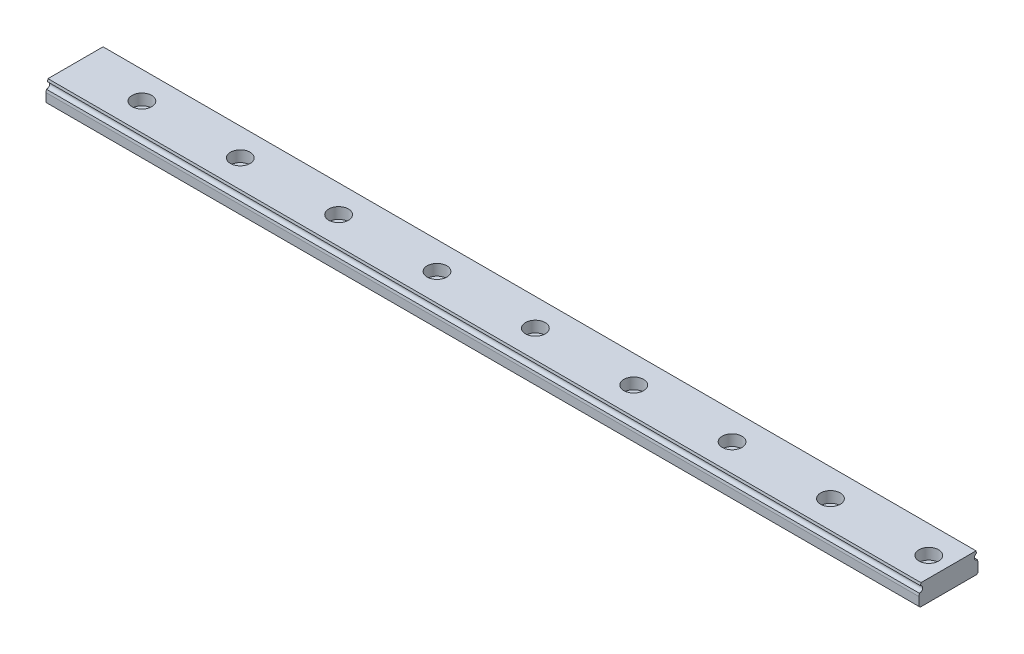
SolidWorks part; units mm, degrees
ref_plane "Plano frontal" through (0, 0, 0) normal (0, 0, 1) x (1, 0, 0)
ref_plane "Plano superior" through (0, 0, 0) normal (0, 1, 0) x (1, 0, 0)
ref_plane "Plano direito" through (0, 0, 0) normal (1, 0, 0) x (0, 0, -1)
ref_plane "Plano1" through (-15, 0, 0) normal (1, 0, 0) x (0, 0, -1)
sketch "Esboço1" plane through (-15, 0, 0) normal (1, 0, 0) x (0, 0, -1)
  line L0 (-12, 4) -> (-12, 0.5)
  line L1 (-12, 0.5) -> (-11.5, 0)
  line L2 (-11.5, 0) -> (11.5, 0)
  line L3 (11.5, 0) -> (12, 0.5)
  line L4 (12, 0.5) -> (12, 4)
  line L5 (12, 4) -> (11.8146, 5.0517)
  line L6 (11.3837, 7.4951) -> (11.2065, 8.5)
  line L7 (11.2065, 8.5) -> (-11.2065, 8.5)
  line L8 (-11.2065, 8.5) -> (-11.3837, 7.4951)
  line L9 (-11.8146, 5.0517) -> (-12, 4)
  arc A0 (11.8146, 5.0517) -> (11.3837, 7.4951) centre (11.75, 6.3) cw
  arc A1 (-11.3837, 7.4951) -> (-11.8146, 5.0517) centre (-11.75, 6.3) cw
extrude "Ressalto-extrusão1" add sketch "Esboço1" along normal blind 263 and the other way blind 92
ref_plane "Plano2" through (0, 0, 0) normal (0, 0, 1) x (1, 0, 0)
sketch "Esboço2" plane through (0, 0, 0) normal (0, 0, 1) x (1, 0, 0)
  line L0 (0, 8.5) -> (4, 8.5)
  line L1 (4, 8.5) -> (4, 4)
  line L2 (4, 4) -> (2.25, 4)
  line L3 (2.25, 4) -> (2.25, 0)
  line L4 (2.25, 0) -> (0, 0)
  line L5 (0, 0) -> (0, 8.5)
  line L6 (0, 0) -> (0, 8.5) construction
ref_plane "Plano3" through (0, 0, 0) normal (0, 0, 1) x (1, 0, 0)
sketch "Esboço3" plane through (0, 0, 0) normal (0, 0, 1) x (1, 0, 0)
  line L0 (40, 8.5) -> (44, 8.5)
  line L1 (44, 8.5) -> (44, 4)
  line L2 (44, 4) -> (42.25, 4)
  line L3 (42.25, 4) -> (42.25, 0)
  line L4 (42.25, 0) -> (40, 0)
  line L5 (40, 0) -> (40, 8.5)
  line L6 (40, 0) -> (40, 8.5) construction
revolve "Corte-Revolução2" cut sketch "Esboço3" angle 360 about L6 reverse direction yes
pattern_linear "LPattern1" count 6 spacing 40 along (1, 0, 0) count 4 spacing 40 along (-1, 0, 0) of "Corte-Revolução2"
